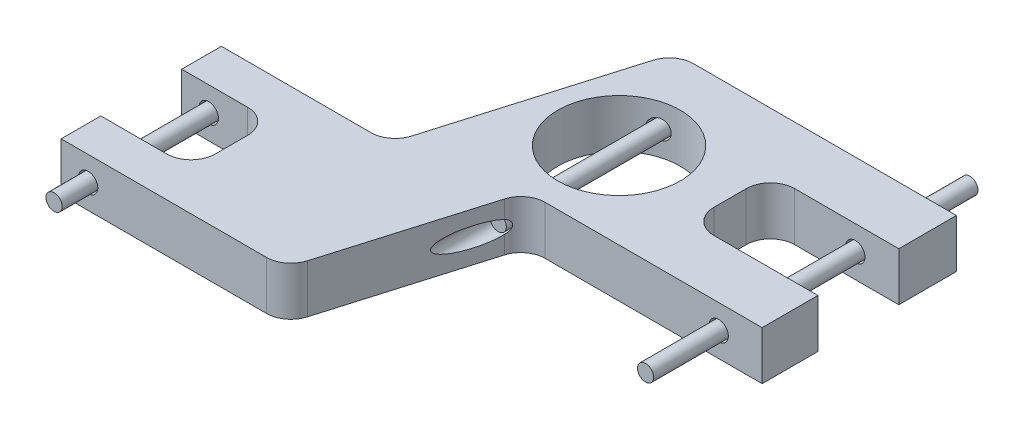
SolidWorks part; units mm, degrees
note: The reader was unsure of these and kept them because the rebuilt part matched: shared geometry of "Sketch24<3>", "Sketch24<4>".
ref_plane "Front Plane" through (0, 0, 0) normal (0, 0, 1) x (1, 0, 0)
ref_plane "Top Plane" through (0, 0, 0) normal (0, 1, 0) x (1, 0, 0)
ref_plane "Right Plane" through (0, 0, 0) normal (1, 0, 0) x (0, 0, -1)
sketch "Sketch21" plane through (0, 0, 0) normal (0, 1, 0) x (1, 0, 0)
  line L0 (-68.3493, -4.0266) -> (-58.0049, -4.0266)
  line L1 (-54.1949, -7.8366) -> (-54.1949, -12.9166)
  line L2 (-58.0049, -16.7266) -> (-68.3493, -16.7266)
  line L3 (-68.3493, -16.7266) -> (-68.3493, -22.9496)
  line L4 (12.3038, 6.3892) -> (12.3038, 15.134)
  line L5 (-68.3493, -22.9496) -> (-36.1125, -22.9496)
  line L6 (-68.3493, -4.0266) -> (-68.3493, 2.1964)
  line L7 (12.3038, 27.834) -> (-4.0242, 27.834)
  line L8 (52.8639, 77.8829) -> (52.8639, -77.8829) construction
  line L9 (12.3038, 6.3892) -> (-21.7488, 6.3892)
  line L10 (-7.8342, 24.024) -> (-7.8342, 18.944)
  line L11 (-4.0242, 15.134) -> (12.3038, 15.134)
  line L12 (12.3038, 27.834) -> (12.3038, 36.8724)
  line L14 (-41.2327, 4.9267) -> (-32.5996, 34.1421)
  line L15 (-28.9458, 36.8724) -> (12.3038, 36.8724)
  line L16 (-25.4027, 3.6589) -> (-32.4586, -20.2193)
  line L17 (-68.3493, 2.1964) -> (-44.8866, 2.1964)
  circle A0 centre (-23.6637, 19.9075) radius 9.619
  circle A1 centre (-23.6637, 19.9075) radius 17.239 construction
  arc A2 (-32.5996, 34.1421) -> (-28.9458, 36.8724) centre (-28.9458, 33.0624) cw
  arc A3 (-44.8866, 2.1964) -> (-41.2327, 4.9267) centre (-44.8866, 6.0064) ccw
  arc A4 (-32.4586, -20.2193) -> (-36.1125, -22.9496) centre (-36.1125, -19.1396) cw
  arc A5 (-25.4027, 3.6589) -> (-21.7488, 6.3892) centre (-21.7488, 2.5792) cw
  arc A6 (-58.0049, -4.0266) -> (-54.1949, -7.8366) centre (-58.0049, -7.8366) cw
  arc A7 (-54.1949, -12.9166) -> (-58.0049, -16.7266) centre (-58.0049, -12.9166) cw
  arc A8 (-4.0242, 27.834) -> (-7.8342, 24.024) centre (-4.0242, 24.024) ccw
  arc A9 (-7.8342, 18.944) -> (-4.0242, 15.134) centre (-4.0242, 18.944) ccw
  point P35 (-54.1949, -4.0266)
  point P38 (-54.1949, -16.7266)
  point P39 (-7.8342, 27.834)
  point P42 (-7.8342, 15.134)
  dimension "D7" = 7.62
  dimension "D5" = 3.81
  dimension "D1" = 3.81
  dimension "D2" = 12.7
  dimension "D3" = 12.7
  dimension "D4" = 30.4831
  dimension "D8" = 6.223
extrude "Extrude1" add sketch "Sketch21" along normal mid plane 7.62
sketch "Sketch22" plane through (0, 0, -36.8724) normal (0, 0, -1) x (-1, 0, 0)
  line L0 (29.6119, 0) -> (68.3493, 0) construction
  line L1 (29.6119, 3.81) -> (29.6119, -3.81) construction
  line L2 (68.3493, 3.81) -> (68.3493, -3.81) construction
  circle A0 centre (-5.4792, 0) radius 1.524
  circle A1 centre (64.1168, 0) radius 1.524
  circle A2 centre (26.5284, 0) radius 1.524
  dimension "D1" = 69.596
  dimension "D2" = 3.048
extrude "Cut-Extrude1" cut sketch "Sketch22" against normal mid plane 183.515
sketch "Sketch24" plane through (0, 0, 0) normal (0, 0, 1) x (1, 0, 0)
  circle A0 centre (-26.5284, 0) radius 1.27
  circle A1 centre (-64.1168, 0) radius 1.27
  circle A2 centre (5.4792, 0) radius 1.27
  dimension "D1" = 2.54
extrude "Extrude2" add sketch "Sketch24" against normal blind 34.29 from offset 3.81 separate body contours A0
extrude "Extrude3" add sketch "Sketch24<3>" along normal blind 28.288 separate body contours A1
sketch "Sketch24<3>" plane through (0, 0, 0) normal (0, 0, 1) x (1, 0, 0) same geometry as "Sketch24"
extrude "Extrude4" add sketch "Sketch24<4>" against normal blind 50.894 from offset 5.08 separate body contours A2
sketch "Sketch24<4>" plane through (0, 0, 0) normal (0, 0, 1) x (1, 0, 0) same geometry as "Sketch24"
